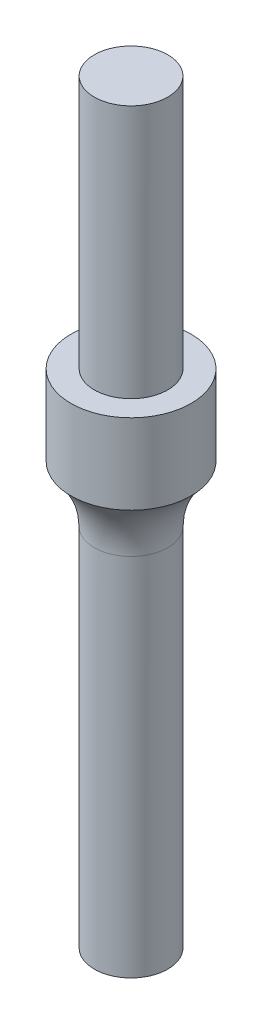
SolidWorks part; units mm, degrees
ref_plane "Спереди" through (0, 0, 0) normal (0, 0, 1) x (1, 0, 0)
ref_plane "Сверху" through (0, 0, 0) normal (0, 1, 0) x (1, 0, 0)
ref_plane "Справа" through (0, 0, 0) normal (1, 0, 0) x (0, 0, -1)
sketch "Эскиз1" plane through (0, 0, -25.3) normal (0, 0, -1) x (-1, 0, 0)
  line L1 (-39, 12.7) -> (-49, 12.7) construction
  line L3 (-39, -6.0912) -> (-39, 19.7)
  line L4 (-37.4, 15.7) -> (-40.6, 15.7) construction
  line L5 (-37.4, 15.7) -> (-40.6, 15.7) construction
  line L6 (-39, 12.7) -> (-49, 12.7) construction
  line L10 (-37.5, -6.0912) -> (-40.5, -6.0912) construction
  line L11 (-39, -6.0912) -> (-40.5, -6.0912) construction
  line L12 (-39, 15.7) -> (-39, -6.0912) construction
  line L13 (-39, -6.0912) -> (-40.375, -6.0912)
  line L14 (-40.375, -6.0912) -> (-40.375, 9.7)
  line L15 (-40.375, 9.7) -> (-41.25, 9.7)
  line L16 (-41.25, 9.7) -> (-41.25, 12.7)
  line L17 (-41.25, 12.7) -> (-40.375, 12.7)
  line L18 (-40.375, 12.7) -> (-40.375, 19.7)
  line L19 (-40.375, 19.7) -> (-39, 19.7)
  line L20 (-39, 15.7) -> (-39, 19.7) construction
  dimension "D1" = 1.375
  dimension "D2" = 4
  dimension "D4" = 2.25
  dimension "D5" = 3
revolve "Повернуть1" add sketch "Эскиз1" angle 360 about L3 other way angle 360
fillet "Скругление1" radius 3 1 edges at (39, 9.7, -26.675)
sketch "Эскиз3" plane through (0, 19.7, 0) normal (0, 1, 0) x (1, 0, 0)
  circle A1 centre (39, 25.3) radius 1.375
  circle A2 centre (39, 25.3) radius 1.375
  dimension "D1" = 0
extrude "Бобышка-Вытянуть2" add sketch "Эскиз3" along normal blind 2.5
